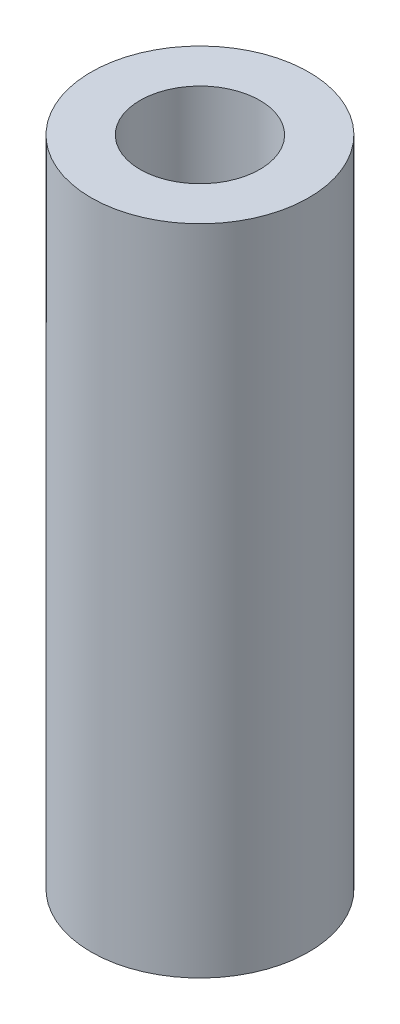
SolidWorks part; units mm, degrees
ref_plane "Front Plane" through (0, 0, 0) normal (0, 0, 1) x (1, 0, 0)
ref_plane "Top Plane" through (0, 0, 0) normal (0, 1, 0) x (1, 0, 0)
ref_plane "Right Plane" through (0, 0, 0) normal (1, 0, 0) x (0, 0, -1)
sketch "Sketch1" plane through (0, 0, 0) normal (0, 1, 0) x (1, 0, 0)
  circle A0 centre (0, 0) radius 5.5
  circle A1 centre (0, 0) radius 10
  dimension "D1" = 11
  dimension "D2" = 20
extrude "Boss-Extrude1" add sketch "Sketch1" along normal blind 60
extrude "Boss-Extrude2" add sketch "Sketch1<2>" along normal blind 10 contours A0
sketch "Sketch1<2>" plane through (0, 0, 0) normal (0, 1, 0) x (1, 0, 0) same geometry as "Sketch1"
equation "\"shaftDiam\" = 20mm"
equation "\"keyW\" = 8mm"
equation "\"keyL\" = 10mm"
equation "\"clearance\" = 1mm"
equation "\"handleShaftLen\" = 60mm"
equation "\"panelH\" = 80mm"
equation "\"panelW\" = 110mm"
equation "\"D1@Sketch1\"=\"clearance\"+\"shaftDiam\"/2"
equation "\"D2@Sketch1\"=\"shaftDiam\""
equation "\"D1@Boss-Extrude1\"= \"panelH\" - \"shaftDiam\""
